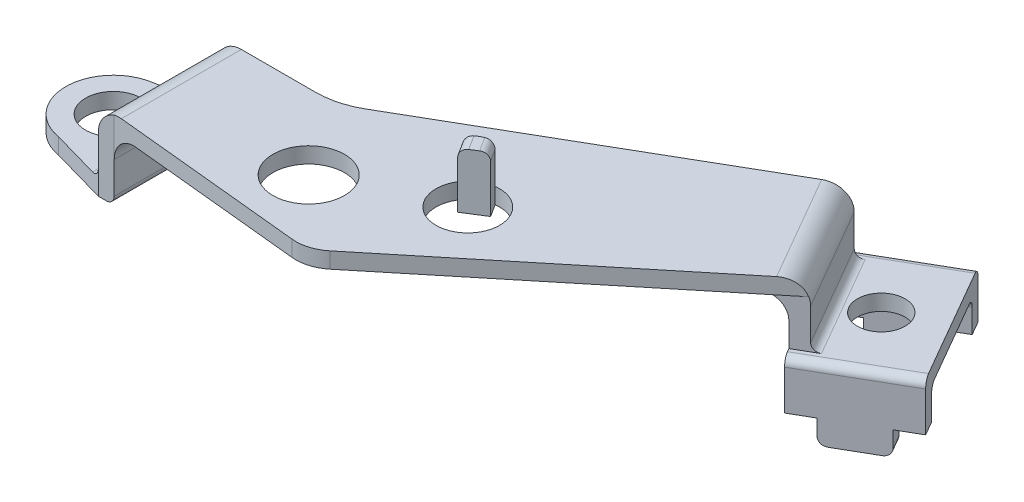
SolidWorks part; units mm, degrees
ref_plane "Front Plane" through (0, 0, 0) normal (0, 0, 1) x (1, 0, 0)
ref_plane "Top Plane" through (0, 0, 0) normal (0, 1, 0) x (1, 0, 0)
ref_plane "Right Plane" through (0, 0, 0) normal (1, 0, 0) x (0, 0, -1)
sketch "Sketch2" plane through (0, 0, 0) normal (0, 1, 0) x (1, 0, 0)
  line L0 (0, 0) -> (10.3205, 0)
  line L1 (15.3205, 1.3397) -> (54.2917, 23.8397)
  line L2 (54.2917, 23.8397) -> (61.7917, 10.8494)
  line L3 (61.7917, 10.8494) -> (28.5157, -16.385)
  line L4 (24.8763, -17.4837) -> (0, -15)
  line L5 (0, -15) -> (0, 0)
  arc A0 (10.3205, 0) -> (15.3205, 1.3397) centre (10.3205, 10) ccw
  arc A3 (28.5157, -16.385) -> (24.8763, -17.4837) centre (25.3698, -12.5412) cw
  point P6 (13, 0)
  point P15 (-1.3167, -8.2658)
  dimension "D6" = 43
  dimension "D9" = 10
  dimension "D1" = 15
  dimension "D2" = 135
  dimension "D3" = 150
  dimension "D4" = 15
  dimension "D5" = 45
  dimension "D7" = 25
  dimension "D8" = 13
extrude "Boss-Extrude1" add sketch "Sketch2" along normal blind 2 contours A3 L3 L2 L1 L0 L5 L4 region at (30.3937, 0, -0.0934)
sketch "Sketch3" plane through (51.0417, 0, -29.4689) normal (0.866, 0, -0.5) x (-0.5, 0, -0.866)
  line L0 (-21.5, 0) -> (-21.5, -8)
  line L1 (-6.5, 0) -> (-6.5, -8)
  line L2 (-6.5, -8) -> (-21.5, -8)
  line L7 (-21.5, 0) -> (-6.5, 0)
  line L8 (-6.5, 0) -> (-6.5, 2)
  line L9 (-6.5, 2) -> (-21.5, 2)
  line L10 (-21.5, 2) -> (-21.5, 0)
  line L11 (-21.5, 0) -> (-6.5, 0)
  dimension "D1" = 10
  dimension "D2" = 0
extrude "Boss-Extrude2" add sketch "Sketch3" against normal blind 2
ref_plane "Plane1" through (0, -6, 0) normal (0, -1, 0) x (-1, 0, 0)
fillet "Fillet2" radius 3 2 edges at (58.0417, 2, -17.3446)
sketch "Sketch4" plane through (0, -8, 0) normal (0, -1, 0) x (1, 0, 0)
  line L0 (60.0596, -9.8494) -> (60.8096, -8.5503)
  line L1 (60.8096, -8.5503) -> (72.0679, -15.0503)
  line L2 (72.0679, -15.0503) -> (63.0679, -30.6388)
  line L3 (63.0679, -30.6388) -> (51.8096, -24.1388)
  line L4 (51.8096, -24.1388) -> (52.5596, -22.8397)
  line L5 (60.0596, -9.8494) -> (52.5596, -22.8397) construction
  line L6 (57.4388, -27.3888) -> (66.4388, -11.8003) construction
  line L7 (67.5679, -22.8446) -> (61.9388, -19.5946) construction
  line L8 (52.5596, -22.8397) -> (60.0596, -9.8494)
  circle A0 centre (61.9388, -19.5946) radius 3
  dimension "D3" = 6
  dimension "D1" = 18
  dimension "D2" = 13
sketch "Sketch5" plane through (0, -6, 0) normal (0, -1, 0) x (-1, 0, 0)
  line L0 (-60.8096, 8.5503) -> (-72.0679, 15.0503) construction
  line L1 (-72.0679, 15.0503) -> (-63.0679, 30.6388) construction
  line L2 (-67.5679, 22.8446) -> (-61.9388, 19.5946) construction
  line L3 (-57.4388, 27.3888) -> (-66.4388, 11.8003) construction
  line L4 (-63.0679, 30.6388) -> (-51.8096, 24.1388) construction
  line L5 (-51.8096, 24.1388) -> (-52.5596, 22.8397) construction
  line L6 (-52.5596, 22.8397) -> (-60.0596, 9.8494) construction
  line L7 (-60.0596, 9.8494) -> (-60.8096, 8.5503) construction
  line L8 (-60.8096, 8.5503) -> (-72.0679, 15.0503)
  line L9 (-72.0679, 15.0503) -> (-63.0679, 30.6388)
  line L10 (-67.5679, 22.8446) -> (-61.9388, 19.5946)
  line L11 (-57.4388, 27.3888) -> (-66.4388, 11.8003)
  line L12 (-63.0679, 30.6388) -> (-51.8096, 24.1388)
  line L13 (-51.8096, 24.1388) -> (-52.5596, 22.8397)
  line L14 (-52.5596, 22.8397) -> (-60.0596, 9.8494)
  line L15 (-60.0596, 9.8494) -> (-60.8096, 8.5503)
  circle A0 centre (-61.9388, 19.5946) radius 3 construction
  circle A1 centre (-61.9388, 19.5946) radius 3
extrude "Boss-Extrude4" add sketch "Sketch5" along normal blind 2 contours A1 L11 L12 L9 L10 | A1 L11 L8 L15 L14 L13 L12 | A1 L10 L9 L8 L11 region at (58.8889, -6, -17.8337) region at (67.4604, -6, -17.0742) region at (62.5169, -6, -25.6366)
fillet "Fillet3" radius 1 2 edges at (58.0417, -6, -17.3446) (56.3096, -8, -16.3446)
sketch "Sketch6" plane through (11.5, 0, 19.9186) normal (0.5, 0, 0.866) x (0.866, 0, -0.5)
  line L1 (56.9378, -6) -> (56.9378, -12)
  line L2 (56.9378, -12) -> (59.9378, -12)
  line L3 (59.9378, -12) -> (59.9378, -14)
  line L4 (60.9378, -15) -> (65.9378, -15)
  line L5 (66.9378, -14) -> (66.9378, -12)
  line L6 (66.9378, -12) -> (69.9378, -12)
  line L7 (69.9378, -12) -> (69.9378, -6)
  line L8 (56.9378, -6) -> (69.9378, -6) construction
  line L9 (69.9378, -8) -> (69.9378, -6) construction
  line L11 (56.9378, -6) -> (69.9378, -6)
  line L12 (69.9378, -6) -> (68.2065, -5.9926)
  arc A0 (65.9378, -15) -> (66.9378, -14) centre (65.9378, -14) ccw
  arc A1 (59.9378, -14) -> (60.9378, -15) centre (60.9378, -14) ccw
  arc M2 (56.9378, -7) -> (57.9378, -8) centre (57.9378, -7) ccw
  line M3 (57.9378, -8) -> (69.9378, -8)
  dimension "D5" = 1
  dimension "D1" = 6
  dimension "D2" = 6
  dimension "D3" = 3
  dimension "D4" = 9
extrude "Boss-Extrude5" add sketch "Sketch6" against normal blind 2 contours L3 A1 L4 A0 L5 L6 L7 L1 L2 M3 M2 region at (66.4227, -10.9751, -11.7911)
sketch "Sketch7" plane through (2.5, 0, 4.3301) normal (-0.5, 0, -0.866) x (-0.866, 0, 0.5)
  line L0 (-60.9378, -15) -> (-65.9378, -15) construction
  line L1 (-60.9378, -15) -> (-65.9378, -15)
  line L3 (-66.9378, -14) -> (-66.9378, -12) construction
  line L4 (-69.9378, -8) -> (-57.9378, -8)
  line L5 (-56.9378, -7) -> (-56.9378, -6)
  line L6 (-56.9378, -6) -> (-69.9378, -6)
  line L7 (-69.9378, -6) -> (-69.9378, -8)
  line L8 (-69.9378, -8) -> (-57.9378, -8)
  line L9 (-56.9378, -7) -> (-56.9378, -6)
  line L10 (-56.9378, -6) -> (-69.9378, -6)
  line L11 (-69.9378, -6) -> (-69.9378, -8)
  line L12 (-66.9378, -12) -> (-69.9378, -12) construction
  line L13 (-59.9378, -12) -> (-59.9378, -14) construction
  line L14 (-56.9378, -12) -> (-59.9378, -12) construction
  line L16 (-69.9378, -12) -> (-69.9378, -6)
  line L17 (-66.9378, -14) -> (-66.9378, -12)
  line L18 (-66.9378, -12) -> (-69.9378, -12)
  line L19 (-59.9378, -12) -> (-59.9378, -14)
  line L20 (-56.9378, -12) -> (-59.9378, -12)
  line L21 (-56.9378, -12) -> (-56.9378, -6)
  arc A0 (-66.9378, -14) -> (-65.9378, -15) centre (-65.9378, -14) ccw construction
  arc A1 (-57.9378, -8) -> (-56.9378, -7) centre (-57.9378, -7) ccw
  arc A2 (-57.9378, -8) -> (-56.9378, -7) centre (-57.9378, -7) ccw
  arc A3 (-60.9378, -15) -> (-59.9378, -14) centre (-60.9378, -14) ccw construction
  arc A4 (-66.9378, -14) -> (-65.9378, -15) centre (-65.9378, -14) ccw
  arc A5 (-60.9378, -15) -> (-59.9378, -14) centre (-60.9378, -14) ccw
  line M6 (-69.9378, -8) -> (-57.9378, -8)
  arc M7 (-57.9378, -8) -> (-56.9378, -7) centre (-57.9378, -7) ccw
  dimension "D1" = 0
extrude "Boss-Extrude6" add sketch "Sketch7" against normal blind 2 contours L1 A5 L19 L20 L21 L16 L18 L17 A4 M7 M6 region at (57.4227, -10.9751, -27.3795)
fillet "Fillet5" radius 1 6 edges at (60.0633, -7.7071, -10.4288) (53.0633, -7.7071, -22.5532) (66.4388, -6, -11.8003) (65.8718, -8, -13.7824) (58.8718, -8, -25.9067) (57.4388, -6, -27.3888)
sketch "Sketch8" plane through (0, 0, 0) normal (-1, 0, 0) x (0, 0, 1)
  line L0 (0, 2) -> (0, -8)
  line L1 (0, -8) -> (15, -8)
  line L2 (15, -8) -> (15, 2)
  line L3 (0, 2) -> (15, 2)
  dimension "D1" = 10
  dimension "D4" = 8
extrude "Boss-Extrude7" add sketch "Sketch8" along normal blind 2
fillet "Fillet6" radius 3 2 edges at (-2, 2, 7.5)
sketch "Sketch9" plane through (0, -8, 0) normal (0, -1, 0) x (1, 0, 0)
  line L0 (-2, 0) -> (-9, 1.1832)
  line L1 (-2, 15) -> (-9, 13.0154)
  line L2 (-2, 0) -> (-2, 15) construction
  line L4 (-2, 15) -> (-2, 0)
  arc A0 (-9, 13.0154) -> (-9, 1.1832) centre (-8, 7.0993) ccw
  circle A1 centre (-8, 7.0993) radius 3.5
  dimension "D2" = 7
  dimension "D3" = 6
  dimension "D5" = 6
  dimension "D1" = 7
  dimension "D4" = 7
extrude "Boss-Extrude8" add sketch "Sketch9" against normal blind 2
fillet "Fillet7" radius 1 2 edges at (-2, -6, 7.5) (0, -8, 7.5)
sketch "Sketch12" plane through (0, 2, 0) normal (0, 1, 0) x (1, 0, 0)
  line L0 (1, -7.6498) -> (18.9109, -9.438) construction
  line L2 (24.8763, -17.4837) -> (1, -15.0998) construction
  line L4 (1, 0) -> (1, -15.0998) construction
  circle A0 centre (18.9109, -9.438) radius 4.5
  circle A1 centre (32.424, -2.9267) radius 4
  dimension "D2" = 9
  dimension "D3" = 8
  dimension "D4" = 15
  dimension "D1" = 18
extrude "Cut-Extrude1" cut sketch "Sketch12" against normal blind 10
sketch "Sketch11" plane through (0, 0, 0) normal (0, -1, 0) x (1, 0, 0)
  line L0 (29.2908, 0.4401) -> (30.3597, 2.1305)
  line L1 (30.3597, 2.1305) -> (32.8953, 0.5273)
  line L2 (32.8953, 0.5273) -> (31.9047, -1.0394)
  line L3 (15.3205, -1.3397) -> (51.6936, -22.3397) construction
  arc A1 (31.9047, -1.0394) -> (29.2908, 0.4401) centre (32.947, 3.8507) cw
  circle A5 centre (32.424, 2.9267) radius 4 construction
  dimension "D5" = 5
  dimension "D1" = 3
  dimension "D2" = 2
  dimension "D3" = 2.305
  dimension "D4" = 1.8536
extrude "Boss-Extrude9" add sketch "Sketch11" against normal blind 7
fillet "Fillet9" radius 1 2 edges at (32.4, 7, -0.2561) (29.8252, 7, 1.2853)
